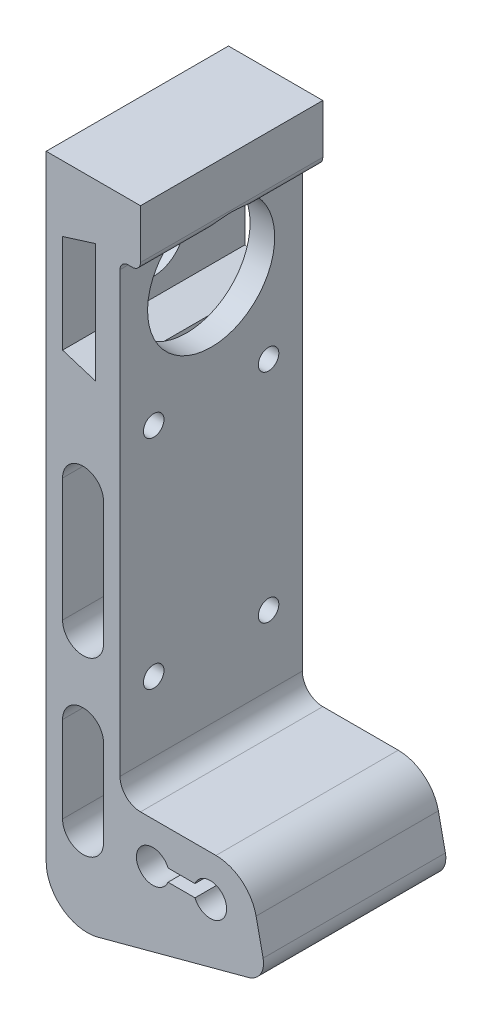
SolidWorks part; units mm, degrees
ref_plane "Front Plane" through (0, 0, 0) normal (0, 0, 1) x (1, 0, 0)
ref_plane "Top Plane" through (0, 0, 0) normal (0, 1, 0) x (1, 0, 0)
ref_plane "Right Plane" through (0, 0, 0) normal (1, 0, 0) x (0, 0, -1)
sketch "Sketch1" plane through (0, 0, 0) normal (0, 0, 1) x (1, 0, 0)
  line L0 (0, 28) -> (0, -122)
  line L1 (12.5882, -131.6593) -> (49.2941, -121.8239)
  line L2 (52.8907, -115.9548) -> (51.1831, -107.9209)
  line L3 (41.4016, -100) -> (23, -100)
  line L4 (18, -95) -> (18, 12)
  line L5 (9, 28) -> (9, -131.9499) construction
  line L6 (0, 28) -> (18, 28)
  line L7 (10, -132) -> (-10.3131, -132) construction
  line L8 (53, -128.0669) -> (53, -89.8097) construction
  line L9 (4, -111) -> (4, -90)
  line L10 (14, -90) -> (14, -111)
  line L11 (9, -69) -> (9, -39) construction
  line L12 (4, -69) -> (4, -39)
  line L13 (14, -69) -> (14, -39)
  line L14 (26, -110) -> (40, -110) construction
  line L15 (29.7081, -108.5) -> (36.2919, -108.5)
  line L16 (29.7081, -111.5) -> (36.2919, -111.5)
  line L17 (4, 12) -> (4, -12)
  line L18 (4, -12) -> (12, -14.5)
  line L19 (12, -14.5) -> (12, 14.5)
  line L20 (12, 14.5) -> (4, 12)
  line L21 (4, 0) -> (12, 0) construction
  line L22 (18, 28) -> (23, 28)
  line L23 (23, 28) -> (23, 16)
  line L24 (21, 14) -> (20, 14)
  arc A0 (0, -122) -> (12.5882, -131.6593) centre (10, -122) ccw
  arc A1 (49.2941, -121.8239) -> (52.8907, -115.9548) centre (48, -116.9943) ccw
  arc A2 (51.1831, -107.9209) -> (41.4016, -100) centre (41.4016, -110) ccw
  arc A3 (23, -100) -> (18, -95) centre (23, -95) cw
  arc A4 (4, -111) -> (14, -111) centre (9, -111) ccw
  arc A5 (14, -90) -> (4, -90) centre (9, -90) ccw
  arc A6 (4, -69) -> (14, -69) centre (9, -69) ccw
  arc A7 (14, -39) -> (4, -39) centre (9, -39) ccw
  arc A8 (29.7081, -108.5) -> (29.7081, -111.5) centre (26, -110) ccw
  arc A9 (36.2919, -111.5) -> (36.2919, -108.5) centre (40, -110) ccw
  arc A10 (20, 14) -> (18, 12) centre (20, 12) ccw
  arc A11 (23, 16) -> (21, 14) centre (21, 16) cw
  point P23 (9, -116)
  point P24 (9, -85)
  point P31 (9, -54)
  point P36 (9, -74)
  point P41 (9, -34)
  point P48 (12, 0)
  point P49 (4, 0)
  point P59 (23, 14)
  dimension "D1" = 10
  dimension "D2" = 160
  dimension "D5" = 5
  dimension "D8" = 5
  dimension "D9" = 10
  dimension "D12" = 10
  dimension "D13" = 10
  dimension "D17" = 5
  dimension "D19" = 8
  dimension "D22" = 8
  dimension "D31" = 2
  dimension "D3" = 53
  dimension "D4" = 18
  dimension "D6" = 32
  dimension "D7" = 15
  dimension "D10" = 12
  dimension "D11" = 28
  dimension "D14" = 31
  dimension "D15" = 16
  dimension "D16" = 11
  dimension "D18" = 40
  dimension "D20" = 26
  dimension "D21" = 10
  dimension "D23" = 40
  dimension "D24" = 3
  dimension "D25" = 24
  dimension "D26" = 29
  dimension "D27" = 8
  dimension "D28" = 4
  dimension "D29" = 5
  dimension "D30" = 14
extrude "Boss-Extrude1" add sketch "Sketch1" along normal mid plane 44.45
sketch "Sketch2" plane through (0, 0, 0) normal (1, 0, 0) x (0, 0, -1)
  line L1 (-14, -25) -> (14, -25) construction
  line L2 (-14, -25) -> (-14, -78) construction
  line L3 (-14, -78) -> (14, -78) construction
  line L4 (14, -25) -> (14, -78) construction
  line L5 (-14, -25) -> (14, -78) construction
  line L6 (-14, -78) -> (14, -25) construction
  circle A0 centre (14, -78) radius 2.5
  circle A1 centre (-14, -78) radius 2.5
  circle A2 centre (-14, -25) radius 2.5
  circle A3 centre (14, -25) radius 2.5
  circle A4 centre (0, 0) radius 15.5
  circle A5 centre (0, 0) radius 7.5
  point P4 (0, -51.5)
  dimension "D4" = 5
  dimension "D5" = 5
  dimension "D6" = 5
  dimension "D7" = 5
  dimension "D8" = 31
  dimension "D9" = 15
  dimension "D1" = 28
  dimension "D2" = 53
  dimension "D3" = 25
extrude "Cut-Extrude5" cut sketch "Sketch2" against normal up to surface (-18 mm away) contours A5 | A3 | A2 | A1 | A0 up to face at (18, -41.5, 0)
extrude "Cut-Extrude7" cut sketch "Sketch2<8>" along normal through all from surface contours A4 starting at face at (12, 0, 7.5)
sketch "Sketch2<8>" plane through (0, 0, 0) normal (1, 0, 0) x (0, 0, -1) same geometry as "Sketch2"
